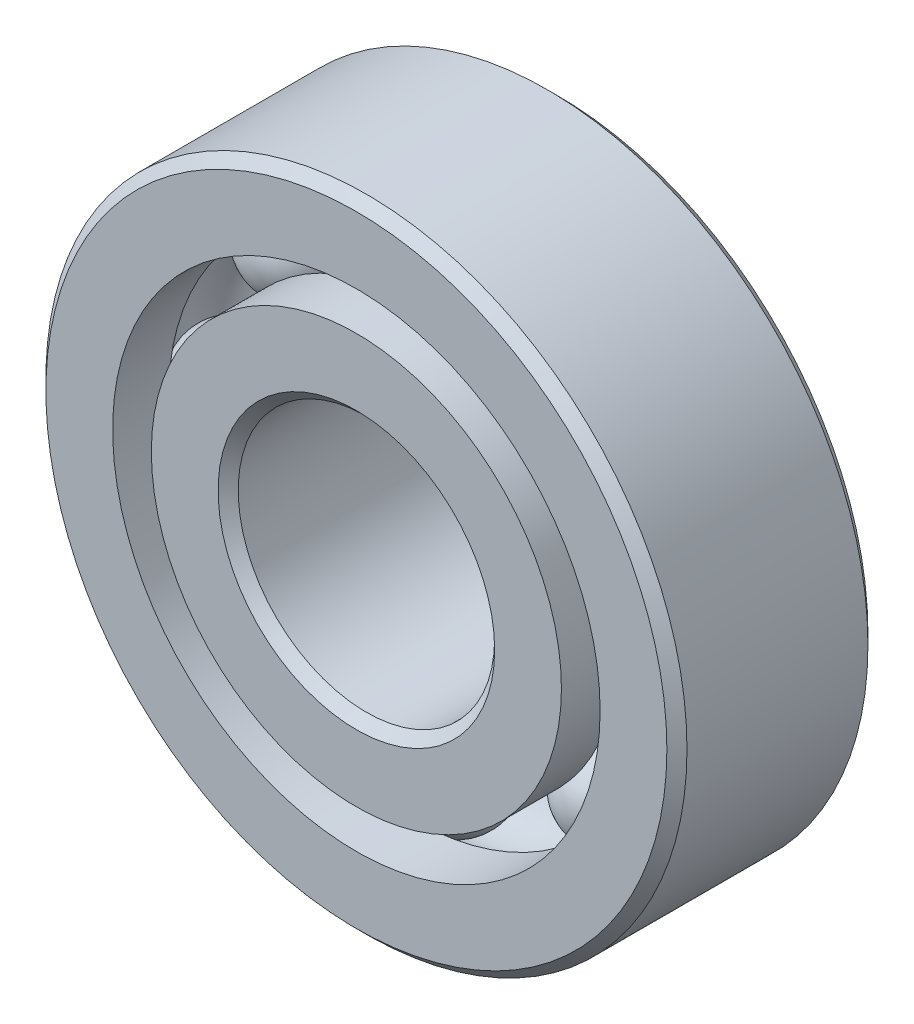
SolidWorks part; units mm, degrees
ref_plane "Front Plane" through (0, 0, 0) normal (0, 0, 1) x (1, 0, 0)
ref_plane "Top Plane" through (0, 0, 0) normal (0, 1, 0) x (1, 0, 0)
ref_plane "Right Plane" through (0, 0, 0) normal (1, 0, 0) x (0, 0, -1)
sketch "Sketch1" plane through (0, 0, 0) normal (1, 0, 0) x (0, 0, -1)
  line L0 (-2.4892, 0) -> (2.4892, 0) construction
  line L1 (0, 7.9375) -> (0, -7.9375) construction
  line L2 (2.2403, 7.9375) -> (-2.2403, 7.9375)
  line L3 (-2.2403, 7.9375) -> (-2.4892, 7.6886)
  line L4 (-2.4892, 7.6886) -> (-2.4892, 6.0352)
  line L5 (-2.4892, 6.0352) -> (-1.1063, 6.0352)
  line L6 (2.4892, 6.0352) -> (1.1063, 6.0352)
  line L7 (2.4892, 7.6886) -> (2.4892, 6.0352)
  line L8 (2.2403, 7.9375) -> (2.4892, 7.6886)
  line L9 (0, 7.9375) -> (0, 5.5562) construction
  line L10 (0, 5.5562) -> (0, 3.175) construction
  arc A0 (-1.1063, 6.0352) -> (1.1063, 6.0352) centre (0, 5.5562) cw
  point P14 (0, 3.175)
  dimension "Width" = 4.9784
  dimension "OD" = 15.875
  dimension "D1" = 45
  dimension "D2" = 0.2489
  dimension "Shaft Dia" = 6.35
  dimension "D3" = 2.2126
  dimension "D4" = 0.479
revolve "Revolve1" add sketch "Sketch1" angle 360 about L0
sketch "Sketch3" plane through (0, 0, 0) normal (1, 0, 0) x (0, 0, -1)
  line L0 (-2.4892, 5.0773) -> (-1.1063, 5.0773)
  line L1 (0, 7.9375) -> (0, -7.9375) construction
  line L2 (-2.4892, 7.6886) -> (-2.4892, 6.0352) construction
  line L3 (-2.4892, 5.0773) -> (-2.4892, 3.4239)
  line L4 (-2.2403, 7.9375) -> (-2.4892, 7.6886) construction
  line L5 (-2.4892, 3.4239) -> (-2.2403, 3.175)
  line L6 (-2.2403, 3.175) -> (2.2403, 3.175)
  line L7 (2.2403, 7.9375) -> (2.2403, -7.9375) construction
  line L8 (2.2403, 3.175) -> (2.4892, 3.4239)
  line L9 (2.4892, -7.6886) -> (2.4892, 7.6886) construction
  line L10 (2.4892, 3.4239) -> (2.4892, 5.0773)
  line L11 (2.4892, 5.0773) -> (1.1063, 5.0773)
  line L13 (2.2403, 7.9375) -> (2.4892, 7.6886) construction
  arc A0 (1.1063, 6.0352) -> (-1.1063, 6.0352) centre (0, 5.5562) ccw construction
  arc A1 (1.1063, 5.0773) -> (-1.1063, 5.0773) centre (0, 5.5562) cw
revolve "Revolve3" add sketch "Sketch3" angle 360 about L0
sketch "Sketch4" plane through (0, 0, 0) normal (1, 0, 0) x (0, 0, -1)
  line L0 (-1.2055, 5.5562) -> (1.2055, 5.5562)
  arc A2 (-1.2055, 5.5562) -> (1.2055, 5.5562) centre (0, 5.5562) cw
  arc A3 (1.1063, 6.0352) -> (-1.1063, 6.0352) centre (0, 5.5562) ccw construction
revolve "Revolve4" add sketch "Sketch4" angle 360 about L0
ref_axis "Axis1" through (0, 0, -2.4892) along (0, 0, 1)
pattern_circular "CirPattern1" count 8 every 45 about axis through (0, 0, -2.4892) along (0, 0, 1) of bodies 104
sketch "Sketch5" plane through (0, 0, 0) normal (1, 0, 0) x (0, 0, -1)
  line L0 (-2.4892, 6.0352) -> (-1.1063, 6.0352) construction
  line L1 (-2.3647, 6.0352) -> (-1.2055, 6.0352)
  line L2 (-2.3647, 6.0352) -> (-2.3647, 5.0773)
  line L3 (-2.3647, 5.0773) -> (-1.2055, 5.0773)
  line L4 (-1.2055, 6.0352) -> (-1.2055, 5.0773)
  line L5 (-2.4892, 5.0773) -> (-1.1063, 5.0773) construction
  line L6 (2.4892, 6.0352) -> (1.1063, 6.0352) construction
  line L7 (2.3647, 6.0352) -> (1.2055, 6.0352)
  line L8 (2.3647, 6.0352) -> (2.3647, 5.0773)
  line L9 (2.3647, 5.0773) -> (1.2055, 5.0773)
  line L10 (1.2055, 6.0352) -> (1.2055, 5.0773)
  line L11 (2.4892, 5.0773) -> (1.1063, 5.0773) construction
  line L12 (-2.2403, 7.9375) -> (-2.4892, 7.6886) construction
  point P18 (-2.3647, 7.813)
revolve "Revolve5" [suppressed] add sketch "Sketch5" angle 360 about L0
equation "\"D2@Sketch1\" = \"Width@Sketch1\"*.05"
equation "\"D3@Sketch1\" = \"Width@Sketch1\"/2.25"
equation "\"D4@Sketch1\" = (((\"OD@Sketch1\"-\"Width@Sketch1\")/2)/3.25)/3.5"
equation "\"D2@CirPattern1\" = 360/\"Balls@CirPattern1\""
